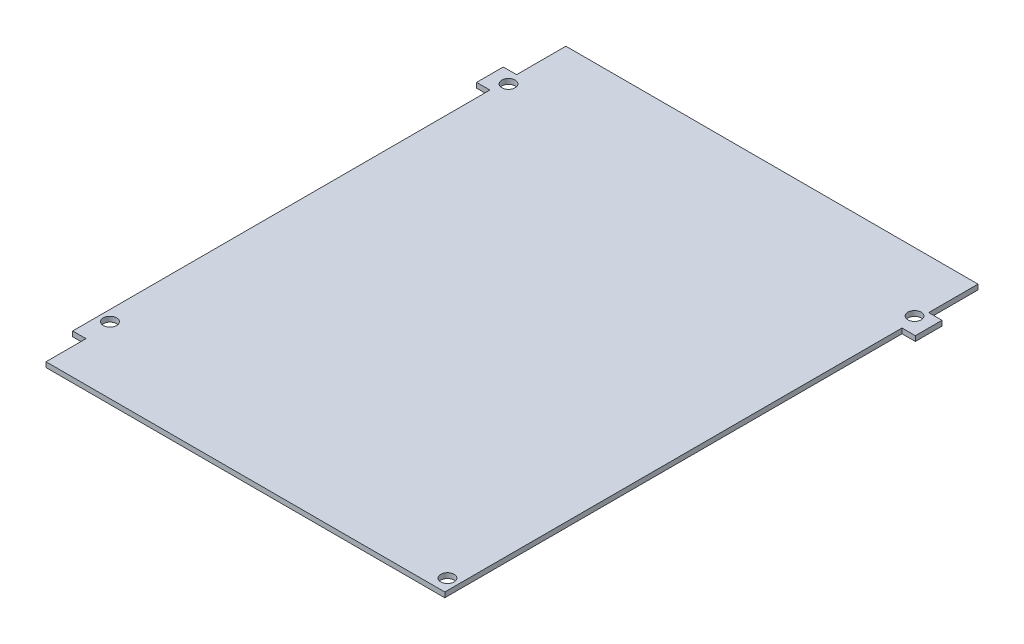
SolidWorks part; units mm, degrees
ref_plane "Front Plane" through (0, 0, 0) normal (0, 0, 1) x (1, 0, 0)
ref_plane "Top Plane" through (0, 0, 0) normal (0, 1, 0) x (1, 0, 0)
ref_plane "Right Plane" through (0, 0, 0) normal (1, 0, 0) x (0, 0, -1)
sketch "Sketch1" plane through (0, 0, 0) normal (0, 1, 0) x (1, 0, 0)
  line L0 (43.0412, 34.2518) -> (48.0412, 34.2518)
  line L1 (-111.5288, 52.7518) -> (43.0412, 52.7518)
  line L2 (-111.5288, 52.7518) -> (-111.5288, 34.2518)
  line L3 (-111.5288, -147.2482) -> (43.0412, -147.2482)
  line L4 (43.0412, 52.7518) -> (43.0412, 34.2518)
  line L5 (48.0412, 34.2518) -> (48.0412, 24.2518)
  line L6 (48.0412, 24.2518) -> (43.0412, 24.2518)
  line L7 (-111.5288, 34.2518) -> (-116.5288, 34.2518)
  line L8 (-116.5288, 34.2518) -> (-116.5288, 24.2518)
  line L9 (-116.5288, 24.2518) -> (-111.5288, 24.2518)
  line L10 (43.0412, 24.2518) -> (43.0412, -147.2482)
  line L11 (-111.5288, 24.2518) -> (-111.5288, -147.2482)
  dimension "D1" = 200
  dimension "D2" = 154.57
  dimension "D3" = 5
  dimension "D4" = 10
base flange "Base-Flange1" sketch "Sketch1" thickness 1.8974 reverse thickness direction no parameters "D1"=2.54
sketch "Sketch6" plane through (0, -1.8974, 0) normal (0, -1, 0) x (1, 0, 0)
  circle A0 centre (-107.5288, 122.2482) radius 2.5
  circle A1 centre (39.0412, 142.2482) radius 2.5
  circle A2 centre (-110.0288, -29.73) radius 2.5
  circle A3 centre (41.5035, -30.5034) radius 2.5
  circle A4 centre (-107.5288, 122.2482) radius 2.5 construction
  circle A5 centre (-110.0288, -29.73) radius 2 construction
  circle A7 centre (39.0412, 142.2482) radius 2 construction
  dimension "D1" = 5
extrude "Cut-Extrude1" cut sketch "Sketch6" against normal blind 1.8974 normal cut yes
sketch "Sketch7" plane through (0, 0, 0) normal (0, 1, 0) x (1, 0, 0)
  line L0 (-111.5288, -132.2482) -> (-106.5288, -132.2482)
  line L1 (-111.5288, 52.7518) -> (-111.5288, 34.2518) construction
  line L2 (-106.5288, -132.2482) -> (-106.5288, -147.2482)
  line L3 (-111.5288, -147.2482) -> (43.0412, -147.2482) construction
  line L4 (-106.5288, -147.2482) -> (-111.5288, -147.2482)
  line L5 (-111.5288, -147.2482) -> (-111.5288, -132.2482)
  dimension "D1" = 5
  dimension "D2" = 15
extrude "Cut-Extrude2" cut sketch "Sketch7" against normal blind 10 normal cut yes
sketch "Bend-Lines1" [suppressed] plane through (0, 0, 0) normal (0, 1, 0) x (1, 0, 0)
sketch "Bounding-Box1" [suppressed] plane through (0, 0, 0) normal (0, 1, 0) x (1, 0, 0)
sheet metal parameters "Sheet-Metal1" thickness 1.8974 parameters "D1"=2.54
flat pattern "Flat-Pattern1" [suppressed]
sketch "Bend-Lines2" plane through (0, 0, 0) normal (0, 1, 0) x (1, 0, 0)
sketch "Bounding-Box2" [suppressed] plane through (0, 0, 0) normal (0, 1, 0) x (1, 0, 0)
sheet metal parameters "Sheet-Metal2" thickness 1.8974 parameters "D1"=2.54
flat pattern "Flat-Pattern1"
sketch "Bend-Lines2" plane through (0, 0, 0) normal (0, 1, 0) x (1, 0, 0)
sketch3d "Bounding-Box2" [suppressed]
  line L0 (-111.5288, 57.7518, 0) -> (-111.5288, -147.2482, 0) construction
  line L1 (38.4712, 57.7518, 0) -> (38.4712, -147.2482, 0) construction
  line L2 (-111.5288, 57.7518, 0) -> (38.4712, 57.7518, 0) construction
  line L3 (-111.5288, -147.2482, 0) -> (38.4712, -147.2482, 0) construction
sheet metal parameters "Sheet-Metal3" thickness 1.8974 parameters "D1"=2.54
flat pattern "Flat-Pattern1"
sketch "Bend-Lines2" plane through (0, 0, 0) normal (0, 1, 0) x (1, 0, 0)
sketch3d "Bounding-Box2" [suppressed]
  line L0 (-116.5288, -147.2482, 0) -> (-116.5288, 47.7518, 0) construction
  line L1 (48.0412, -147.2482, 0) -> (48.0412, 47.7518, 0) construction
  line L2 (-116.5288, -147.2482, 0) -> (48.0412, -147.2482, 0) construction
  line L3 (-116.5288, 47.7518, 0) -> (48.0412, 47.7518, 0) construction
